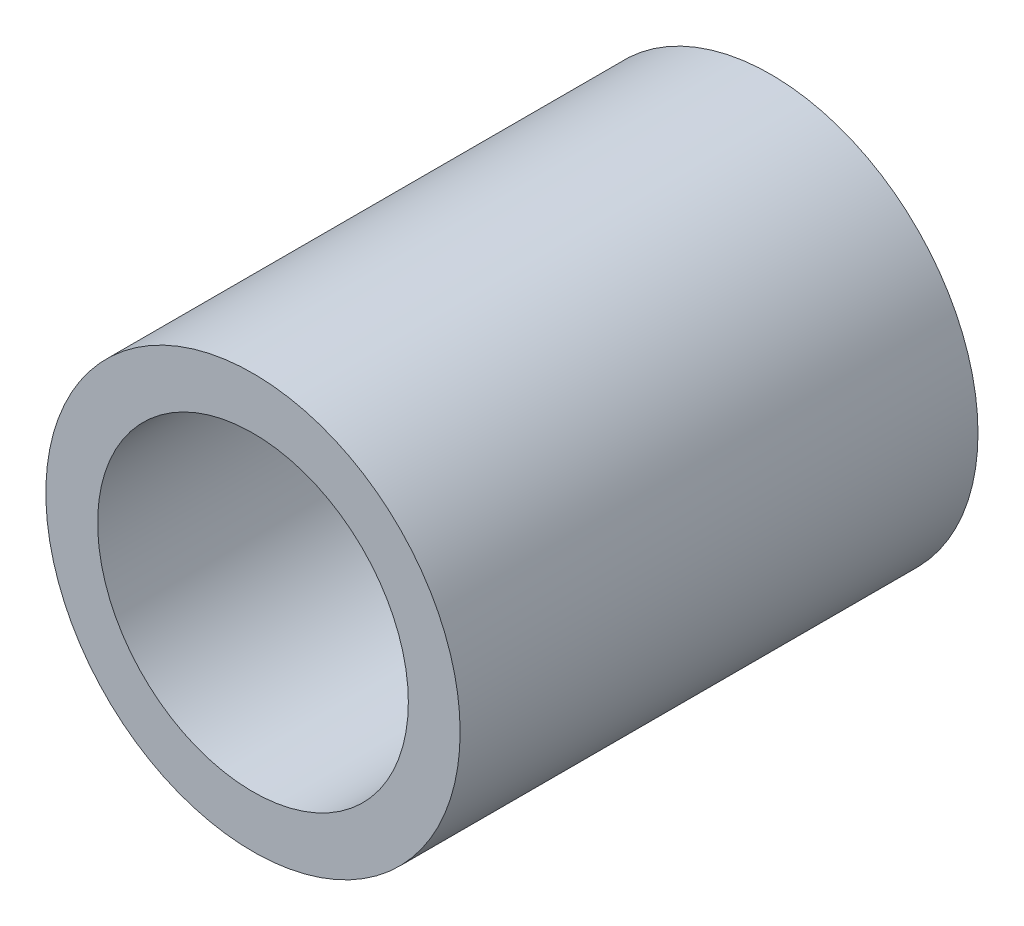
SolidWorks part; units mm, degrees
ref_plane "Front Plane" through (0, 0, 0) normal (0, 0, 1) x (1, 0, 0)
ref_plane "Top Plane" through (0, 0, 0) normal (0, 1, 0) x (1, 0, 0)
ref_plane "Right Plane" through (0, 0, 0) normal (1, 0, 0) x (0, 0, -1)
sketch "Sketch1" plane through (0, 0, 0) normal (0, 0, 1) x (1, 0, 0)
  line L0 (0, 8) -> (0, -8) construction
  line L2 (0, -8.8) -> (0, 8.8) construction
  line L3 (-6, 0) -> (6, 0) construction
  line L4 (8.8, 0) -> (-8.8, 0) construction
  line L5 (0, 0) -> (-20, 0) construction
  point P5 (0, 0)
  point P13 (0, 0)
sketch "Sketch2" plane through (0, 0, 0) normal (0, 0, 1) x (1, 0, 0)
  line L0 (0, 8) -> (0, -8) construction
  circle A0 centre (0, 0) radius 8
  circle A1 centre (0, 0) radius 6
extrude "Boss-Extrude1" add sketch "Sketch2" along normal mid plane 20
ref_plane "Contact Plane 1" through (0, 0, 10) normal (0, 0, 1) x (1, 0, 0)
ref_plane "Contact Plane 2" through (0, 0, -10) normal (0, 0, -1) x (-1, 0, 0)
ref_axis "Center Axis 1" through (0, 0, -10) along (0, 0, 1)
equation "\"D1@Boss-Extrude1\" = \"Length@Sketch1\""
equation "\"D2@Boss-Extrude1\"=\"length@sketch1\"/2"
